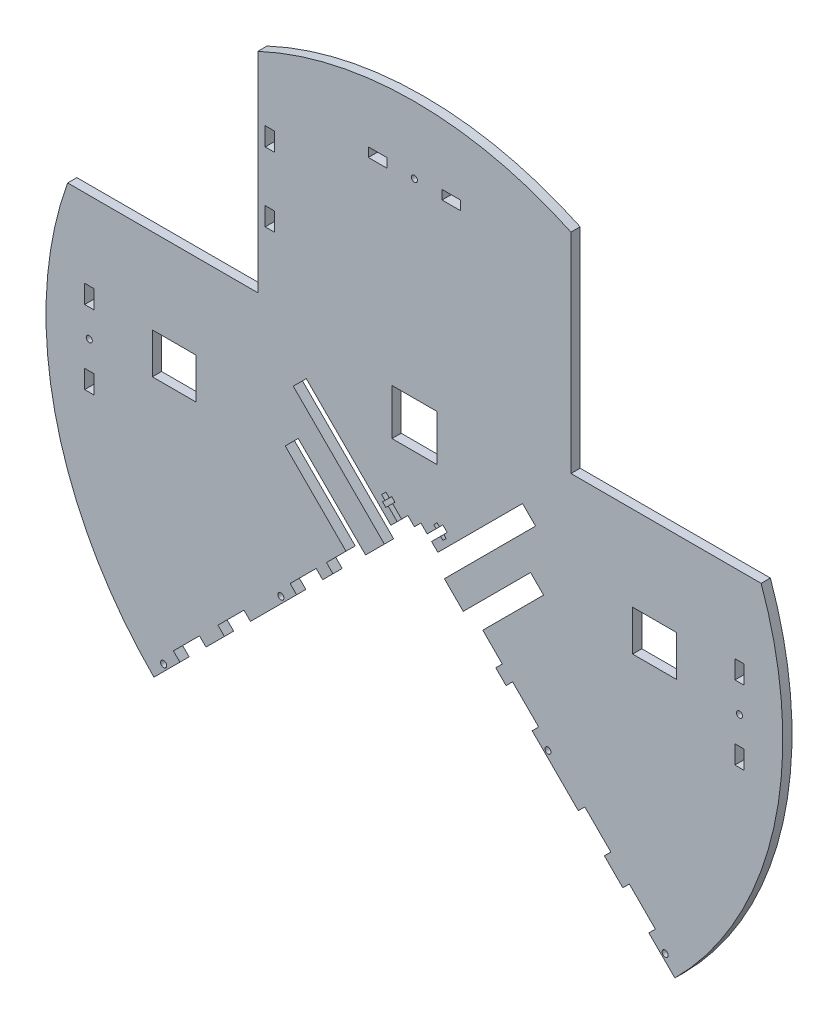
SolidWorks part; units mm, degrees
ref_plane "Front Plane" through (0, 0, 0) normal (0, 0, 1) x (1, 0, 0)
ref_plane "Top Plane" through (0, 0, 0) normal (0, 1, 0) x (1, 0, 0)
ref_plane "Right Plane" through (0, 0, 0) normal (1, 0, 0) x (0, 0, -1)
sketch "Sketch1" plane through (0, 0, 0) normal (0, 0, 1) x (1, 0, 0)
  circle A0 centre (0, -210.9923) radius 254
extrude "Boss-Extrude1" add sketch "Sketch1" along normal blind 6.35 contours A0
sketch "Sketch3" plane through (0, 0, 0) normal (0, 0, -1) x (-1, 0, 0)
  line L0 (179.6051, -390.5974) -> (0, -210.9923)
  line L1 (0, -210.9923) -> (-179.6051, -390.5974)
  line L2 (91.3112, -302.3035) -> (113.0075, -323.9998) construction
  line L3 (-179.6051, -390.5974) -> (-172.1335, -383.1258) construction
  circle A0 centre (0, -210.9923) radius 254 construction
  arc A1 (179.6051, -390.5974) -> (-179.6051, -390.5974) centre (0, -210.9923) cw
extrude "Cut-Extrude1" cut sketch "Sketch3" against normal through all
sketch "Sketch4" plane through (0, 0, 6.35) normal (0, 0, 1) x (1, 0, 0)
  line L0 (-161.6446, -372.6369) -> (-166.1347, -368.1468)
  line L1 (-161.6446, -372.6369) -> (-143.6841, -354.6764)
  line L2 (-166.1347, -368.1468) -> (-148.1742, -350.1862)
  line L3 (-143.6841, -354.6764) -> (-148.1742, -350.1862)
  line L4 (-179.6051, -390.5974) -> (0, -210.9923) construction
  line L5 (-166.1347, -368.1468) -> (-161.6446, -372.6369) construction
  line L7 (-130.9681, -341.9603) -> (-135.4582, -337.4702)
  line L8 (-130.9681, -341.9603) -> (-113.0075, -323.9998)
  line L9 (-135.4582, -337.4702) -> (-117.4977, -319.5097)
  line L10 (-113.0075, -323.9998) -> (-117.4977, -319.5097)
  line L11 (-81.1905, -292.1828) -> (-85.6806, -287.6926)
  line L12 (-81.1905, -292.1828) -> (-63.23, -274.2223)
  line L13 (-85.6806, -287.6926) -> (-67.7201, -269.7321)
  line L14 (-63.23, -274.2223) -> (-67.7201, -269.7321)
  line L15 (-85.6806, -287.6926) -> (-81.1905, -292.1828) construction
  line L17 (-56.1266, -267.1189) -> (-60.6167, -262.6287)
  line L18 (-56.1266, -267.1189) -> (-33.676, -244.6682)
  line L19 (-60.6167, -262.6287) -> (-38.1661, -240.1781)
  line L20 (-33.676, -244.6682) -> (-38.1661, -240.1781)
  line L21 (-11.6893, -222.6816) -> (-16.1795, -218.1915)
  line L22 (-11.6893, -222.6816) -> (0, -210.9923)
  line L23 (-16.1795, -218.1915) -> (-4.4901, -206.5021)
  line L24 (0, -210.9923) -> (-4.4901, -206.5021)
  line L25 (-16.1795, -218.1915) -> (-11.6893, -222.6816) construction
  line L27 (-143.6841, -354.6764) -> (-148.1742, -350.1862) construction
  line L28 (-135.4582, -337.4702) -> (-130.9681, -341.9603) construction
  line L29 (-113.0075, -323.9998) -> (-117.4977, -319.5097) construction
  line L30 (-63.23, -274.2223) -> (-67.7201, -269.7321) construction
  line L31 (0, -210.9923) -> (-4.4901, -206.5021) construction
  line L32 (-60.6167, -262.6287) -> (-38.1661, -240.1781) construction
  line L33 (-60.6167, -262.6287) -> (-56.1266, -267.1189) construction
  line L34 (-38.1661, -240.1781) -> (-33.676, -244.6682) construction
extrude "Cut-Extrude2" cut sketch "Sketch4" against normal through all
mirror "Mirror1" about plane through (0, 0, 0) normal (1, 0, 0) of "Cut-Extrude2"
sketch "Sketch6" plane through (0, 0, 6.35) normal (0, 0, 1) x (1, 0, 0)
  line L0 (-189.391, -362.851) -> (-147.7076, -404.5344) construction
  line L1 (-176.6237, -378.6357) -> (-172.1335, -383.1258) construction
  line L2 (-173.6063, -375.6183) -> (-169.1162, -380.1085) construction
  line L3 (-136.5306, -343.0327) -> (-168.0044, -374.5065) construction
  line L4 (-148.1742, -350.1862) -> (-166.1347, -368.1468) construction
  line L5 (-143.6841, -354.6764) -> (-130.9681, -341.9603) construction
  line L6 (-119.5963, -271.0011) -> (-74.6896, -315.9078) construction
  line L7 (-95.8014, -297.8134) -> (-91.3112, -302.3035) construction
  line L8 (-92.784, -294.796) -> (-88.2939, -299.2862) construction
  circle A0 centre (-172.8699, -379.3721) radius 2.0955
  circle A1 centre (-92.0476, -298.5498) radius 2.0955
  dimension "D1" = 4.191
extrude "Cut-Extrude4" cut sketch "Sketch6" against normal through all
mirror "Mirror2" about plane through (0, 0, 0) normal (1, 0, 0) of "Cut-Extrude4"
sketch "Sketch7" plane through (0, 0, 6.35) normal (0, 0, 1) x (1, 0, 0)
  line L0 (170.4831, -53.7494) -> (119.6731, -104.5593) construction
  line L1 (239.3418, -210.9923) -> (189.3468, -210.9923) construction
  line L2 (0, 19.4565) -> (0, -42.3568) construction
  line L3 (-175.6943, -48.5381) -> (-146.0554, -78.1771) construction
  line L4 (-242.378, -210.9923) -> (-203.5636, -210.9923) construction
  line L5 (-2.1336, -6.35) -> (-2.1336, 0) construction
  line L6 (2.1336, -6.35) -> (2.1336, 0) construction
  line L7 (160.7931, -66.4567) -> (156.303, -70.9468) construction
  line L8 (157.7758, -63.4393) -> (153.2856, -67.9295) construction
  line L9 (220.98, -208.8714) -> (227.33, -208.8714) construction
  line L10 (220.98, -213.1132) -> (227.33, -213.1132) construction
  line L11 (-156.303, -70.9468) -> (-160.7931, -66.4567) construction
  line L12 (-153.2856, -67.9295) -> (-157.7758, -63.4393) construction
  line L13 (-227.33, -213.1132) -> (-220.98, -213.1132) construction
  line L14 (-227.33, -208.8714) -> (-220.98, -208.8714) construction
  line L15 (-224.155, -150.312) -> (-224.155, -266.4456) construction
  line L16 (-118.4045, -28.5582) -> (-198.2831, -108.4368) construction
  line L17 (-31.3546, -3.175) -> (26.462, -3.175) construction
  line L18 (131.6344, -41.7881) -> (173.4787, -83.6324) construction
  line L19 (224.155, -139.5418) -> (224.155, -241.3145) construction
  line L20 (220.98, -179.2423) -> (220.98, -191.9423) construction
  line L21 (227.33, -191.9423) -> (227.33, -179.2423) construction
  line L22 (141.3239, -55.9678) -> (132.3437, -46.9875) construction
  line L23 (145.8141, -51.4776) -> (136.8338, -42.4974) construction
  line L24 (-19.05, 0) -> (-31.75, 0) construction
  line L25 (-31.75, -6.35) -> (-19.05, -6.35) construction
  line L26 (-172.7548, -78.4184) -> (-181.7351, -87.3987) construction
  line L27 (-177.245, -91.8888) -> (-168.2647, -82.9085) construction
  line L28 (-227.33, -179.2423) -> (-227.33, -191.9423) construction
  line L29 (-220.98, -191.9423) -> (-220.98, -179.2423) construction
  circle A0 centre (-224.155, -210.9923) radius 2.0955
  circle A1 centre (-157.0394, -67.1931) radius 2.0955
  circle A2 centre (0, -3.175) radius 2.0955
  circle A3 centre (157.0394, -67.1931) radius 2.0955
  circle A4 centre (224.155, -210.9923) radius 2.0955
  dimension "D1" = 4.191
extrude "Cut-Extrude5" cut sketch "Sketch7" against normal through all
sketch "Sketch8" plane through (0, 0, 6.35) normal (0, 0, 1) x (1, 0, 0)
  line L0 (-20.6696, -231.6619) -> (-11.6893, -222.6816)
  line L1 (-20.6696, -231.6619) -> (-83.5314, -168.8001)
  line L2 (-11.6893, -222.6816) -> (-74.5511, -159.8198)
  line L3 (-83.5314, -168.8001) -> (-74.5511, -159.8198)
  line L4 (-33.676, -244.6682) -> (-11.6893, -222.6816) construction
  line L5 (-8.7612, -234.5899) -> (-94.7474, -148.6038) construction
  line L6 (-77.7195, -170.1218) -> (-52.225, -195.6163) construction
  line L7 (-73.2293, -165.6317) -> (-47.7349, -191.1262) construction
  line L8 (-16.1795, -218.1915) -> (-11.6893, -222.6816) construction
  dimension "D1" = 88.9
extrude "Cut-Extrude6" cut sketch "Sketch8" against normal through all
mirror "Mirror3" about plane through (0, 0, 0) normal (1, 0, 0) of "Cut-Extrude6"
sketch "Sketch9" plane through (0, 0, 6.35) normal (0, 0, 1) x (1, 0, 0)
  line L0 (-28.1989, -194.4827) -> (-15.046, -207.6356) construction
  line L1 (-4.4901, -206.5021) -> (0, -210.9923) construction
  line L2 (-16.1795, -218.1915) -> (-11.6893, -222.6816) construction
  line L3 (-4.4901, -206.5021) -> (-16.1795, -218.1915) construction
  line B0 (-11.8435, -213.8555) -> (-8.8261, -210.8381)
  line B1 (-17.2675, -202.3967) -> (-15.6331, -200.7623)
  line B2 (-15.6331, -200.7623) -> (-13.3881, -203.0073)
  line B3 (-13.3881, -203.0073) -> (-15.0225, -204.6417)
  line B4 (-15.0225, -204.6417) -> (-8.8261, -210.8381)
  line B5 (-17.2675, -202.3967) -> (-19.6024, -200.0618)
  line B6 (-19.6024, -200.0618) -> (-22.6198, -203.0792)
  line B7 (-20.2849, -205.4141) -> (-22.6198, -203.0792)
  line B8 (-18.0398, -207.6591) -> (-11.8435, -213.8555)
  line B9 (-19.6743, -209.2935) -> (-18.0398, -207.6591)
  line B10 (-21.9193, -207.0485) -> (-19.6743, -209.2935)
  line B11 (-20.2849, -205.4141) -> (-21.9193, -207.0485)
sketch_block_instance "TSlot-1"
sketch_block "TSlot" parameters "D1"=3.302, "D2"=3.175
extrude "Cut-Extrude7" cut sketch "Sketch9" against normal through all
mirror "Mirror4" about plane through (0, 0, 0) normal (1, 0, 0) of "Cut-Extrude7"
sketch "Sketch10" plane through (0, 0, 6.35) normal (0, 0, 1) x (1, 0, 0)
  line L0 (-92.7156, -190.1188) -> (-17.7162, -265.1181) construction
  line L1 (-80.0807, -207.2437) -> (-42.6562, -244.6682) construction
  line L2 (-38.1661, -240.1781) -> (-75.5906, -202.7536) construction
  line L3 (-80.0807, -198.2635) -> (-89.061, -207.2437)
  line L4 (-80.0807, -198.2635) -> (-33.676, -244.6682)
  line L5 (-89.061, -207.2437) -> (-42.6562, -253.6485)
  line L6 (-33.676, -244.6682) -> (-42.6562, -253.6485)
  line L7 (-33.676, -244.6682) -> (-20.6696, -231.6619) construction
  line L8 (-75.5906, -202.7536) -> (-80.0807, -207.2437) construction
  dimension "D1" = 6.35
  dimension "D2" = 6.35
extrude "Cut-Extrude8" cut sketch "Sketch10" against normal through all
mirror "Mirror5" about plane through (0, 0, 0) normal (1, 0, 0) of "Cut-Extrude8"
sketch "Sketch11" plane through (0, 0, 6.35) normal (0, 0, 1) x (1, 0, 0)
  line L1 (220.98, -179.2423) -> (227.33, -179.2423)
  line L2 (220.98, -179.2423) -> (220.98, -191.9423)
  line L3 (220.98, -191.9423) -> (227.33, -191.9423)
  line L4 (227.33, -179.2423) -> (227.33, -191.9423)
  line L5 (220.98, -230.0423) -> (227.33, -230.0423)
  line L6 (220.98, -230.0423) -> (220.98, -242.7423)
  line L7 (220.98, -242.7423) -> (227.33, -242.7423)
  line L8 (227.33, -230.0423) -> (227.33, -242.7423)
  line L9 (-227.33, -179.2423) -> (-220.98, -179.2423)
  line L10 (-227.33, -179.2423) -> (-227.33, -191.9423)
  line L11 (-227.33, -191.9423) -> (-220.98, -191.9423)
  line L12 (-220.98, -179.2423) -> (-220.98, -191.9423)
  line L13 (-227.33, -230.0423) -> (-220.98, -230.0423)
  line L14 (-227.33, -230.0423) -> (-227.33, -242.7423)
  line L15 (-227.33, -242.7423) -> (-220.98, -242.7423)
  line L16 (-220.98, -230.0423) -> (-220.98, -242.7423)
  line L17 (-31.75, 0) -> (-19.05, 0)
  line L18 (-31.75, 0) -> (-31.75, -6.35)
  line L19 (-31.75, -6.35) -> (-19.05, -6.35)
  line L20 (-19.05, 0) -> (-19.05, -6.35)
  line L21 (19.05, 0) -> (31.75, 0)
  line L22 (19.05, 0) -> (19.05, -6.35)
  line L23 (19.05, -6.35) -> (31.75, -6.35)
  line L24 (31.75, 0) -> (31.75, -6.35)
extrude "Cut-Extrude9" cut sketch "Sketch11" against normal through all
sketch "Sketch12" plane through (0, 0, 0) normal (0, 0, -1) x (-1, 0, 0)
  line L0 (0, 43.0077) -> (0, -163.8394) construction
  line L1 (107.9506, -125.2137) -> (246.3055, -125.2137)
  line L2 (107.9506, -125.2137) -> (107.9506, 34.5324)
  line L3 (107.9506, 34.5324) -> (246.3055, 34.5324)
  line L4 (246.3055, -125.2137) -> (246.3055, 34.5324)
  line L5 (-246.3055, -125.2137) -> (-246.3055, 34.5324)
  line L6 (-107.9506, 34.5324) -> (-246.3055, 34.5324)
  line L7 (-107.9506, -125.2137) -> (-107.9506, 34.5324)
  line L8 (-107.9506, -125.2137) -> (-246.3055, -125.2137)
  arc A0 (179.6051, -390.5974) -> (-179.6051, -390.5974) centre (0, -210.9923) ccw construction
extrude "Cut-Extrude10" cut sketch "Sketch12" against normal through all
sketch "Sketch13" plane through (0, 0, 6.35) normal (0, 0, 1) x (1, 0, 0)
  line L0 (0, 43.0077) -> (0, -205.8735) construction
  line L1 (-180.6732, -183.7503) -> (-150.4381, -183.7503)
  line L2 (-180.6732, -183.7503) -> (-180.6732, -211.7731)
  line L3 (-180.6732, -211.7731) -> (-150.4381, -211.7731)
  line L4 (-150.4381, -183.7503) -> (-150.4381, -211.7731)
  line L5 (15.4863, -134.3417) -> (15.4863, -166.0517)
  line L6 (15.4863, -134.3417) -> (-15.4863, -134.3417)
  line L7 (0, -134.3417) -> (0, -166.0517)
  line L8 (15.4863, -166.0517) -> (-15.4863, -166.0517)
  line L9 (-15.4863, -134.3417) -> (-15.4863, -166.0517)
  line L11 (150.4381, -183.7503) -> (150.4381, -211.7731)
  line L12 (180.6732, -211.7731) -> (150.4381, -211.7731)
  line L13 (180.6732, -183.7503) -> (180.6732, -211.7731)
  line L14 (180.6732, -183.7503) -> (150.4381, -183.7503)
  arc A0 (107.9506, 18.9265) -> (-107.9506, 18.9265) centre (0, -210.9923) ccw construction
extrude "Cut-Extrude11" cut sketch "Sketch13" against normal through all contours L8 L5 L6 L7 | L6 L9 L8 L7 | L13 L14 L11 L12 | L4 L1 L2 L3 region at (-165.5556, -197.7617, 6.35) region at (7.7431, -150.1967, 6.35) region at (-7.7431, -150.1967, 6.35) region at (165.5556, -197.7617, 6.35)
sketch "Sketch15" plane through (0, 0, 6.35) normal (0, 0, 1) x (1, 0, 0)
  line L0 (-107.9506, -53.1436) -> (107.9506, -53.1436) construction
  line L1 (-107.9506, 18.9265) -> (-107.9506, -125.2137) construction
  line L2 (107.9506, -125.2137) -> (107.9506, 18.9265) construction
  line L3 (-96.5222, -83.3501) -> (-96.5222, -70.6501)
  line L4 (-102.8722, -22.937) -> (-96.5222, -22.937)
  line L5 (-102.8722, -22.937) -> (-102.8722, -35.637)
  line L6 (-102.8722, -35.637) -> (-96.5222, -35.637)
  line L7 (-96.5222, -22.937) -> (-96.5222, -35.637)
  line L8 (-102.8722, -70.6501) -> (-96.5222, -70.6501)
  line L9 (-102.8722, -83.3501) -> (-102.8722, -70.6501)
  line L10 (-102.8722, -83.3501) -> (-96.5222, -83.3501)
  dimension "D1" = 6.35
  dimension "D2" = 12.7
extrude "Cut-Extrude12" cut sketch "Sketch15" against normal through all
